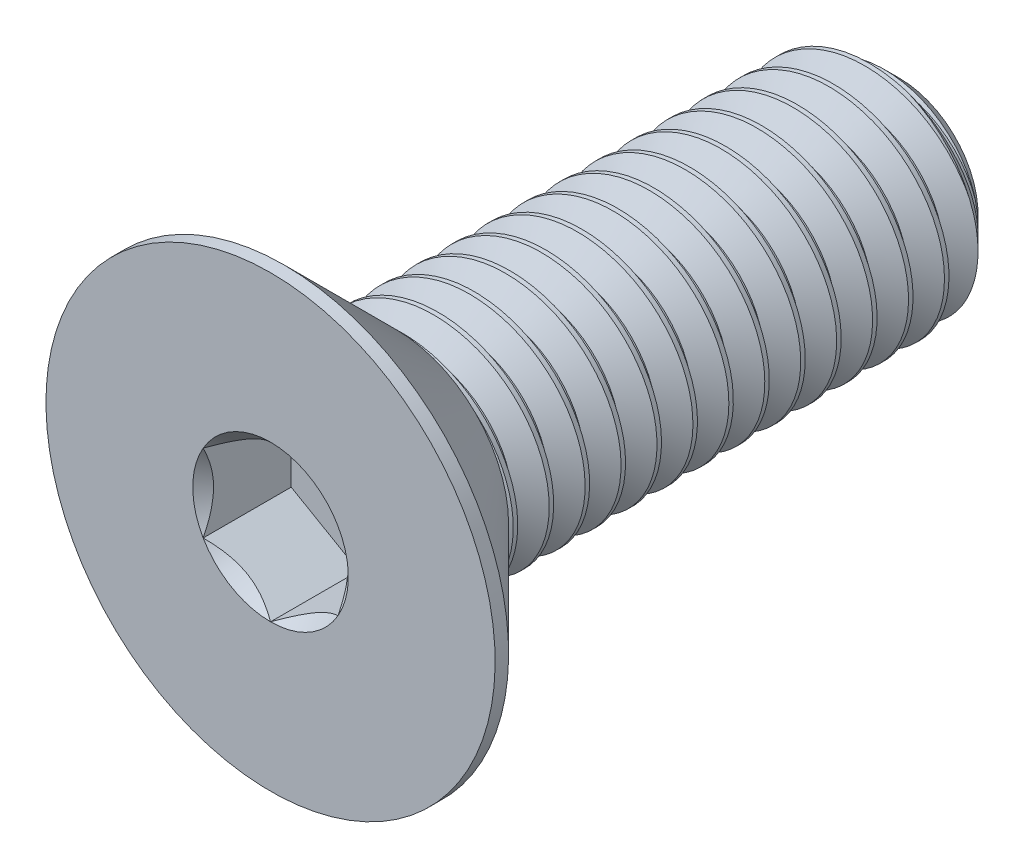
SolidWorks part; units mm, degrees
ref_plane "Front" through (0, 0, 0) normal (0, 0, 1) x (1, 0, 0)
ref_plane "Top" through (0, 0, 0) normal (0, 1, 0) x (1, 0, 0)
ref_plane "Right" through (0, 0, 0) normal (1, 0, 0) x (0, 0, -1)
sketch "Sketch1" plane through (0, 0, 0) normal (1, 0, 0) x (0, 0, -1)
  line L0 (-7, 5) -> (-6.7, 5) construction
  line L1 (-6.7, 5) -> (-4.2, 2.5) construction
  line L2 (-7, 2.5) -> (7, 2.5) construction
  line L3 (7, 2.5) -> (7, 0) construction
  line L4 (7, 0) -> (-7, 0) construction
  line L5 (-7, 0) -> (-7, 5) construction
  line L6 (-7, 5) -> (-7, -5) construction
  line L7 (7, 2.5) -> (7, -2.5) construction
  line L8 (-7, -5) -> (-6.7, -5) construction
  line L9 (-6.7, -5) -> (-4.2, -2.5) construction
  line L11 (-7, 2.5) -> (-7, 0) construction
  line L12 (-4.2, 2.5) -> (-4.2, 0) construction
  line L13 (6.95, 2.5866) -> (7.35, 1.8938) construction
  line L14 (7.35, 1.8938) -> (7.75, 2.5866) construction
  line L15 (7.75, 2.5866) -> (6.95, 2.5866) construction
  line L16 (7.35, 2.5866) -> (7.35, 2.5) construction
  line L17 (7.35, 2.5) -> (7.35, 1.9804) construction
  line L18 (7.35, 1.9804) -> (7.35, 1.8938) construction
  line L19 (7.35, 2.5433) -> (7.725, 2.5433) construction
  line L20 (7.35, 2.5433) -> (6.975, 2.5433) construction
  line L21 (7, 2.5) -> (7.7, 2.5) construction
  line L22 (7.3, 1.9804) -> (7.4, 1.9804) construction
  line L23 (7, -2.5) -> (-4.2, -2.5) construction
  point P10 (5, -2.5)
  point P24 (-4.2, 2.5)
  point P30 (0, 0)
  dimension "Head Diameter" = 10
  dimension "Head Height" = 2.8
  dimension "Length" = 14
  dimension "Countersink Angle" = 90
  dimension "Thread Pitch" = 0.8
  dimension "D2" = 0.1
  dimension "Minimum Thread Length" = 11.2
  dimension "Thread Size" = 5
  dimension "D1" = 2
sketch "Sketch2" plane through (0, 0, 0) normal (0, 0, 1) x (1, 0, 0)
  line L1 (0, 1.7321) -> (-1.5, 0.866) construction
  line L2 (-1.5, 0.866) -> (-1.5, -0.866) construction
  line L3 (-1.5, -0.866) -> (0, -1.7321) construction
  line L4 (0, -1.7321) -> (1.5, -0.866) construction
  line L5 (1.5, -0.866) -> (1.5, 0.866) construction
  line L6 (1.5, 0.866) -> (0, 1.7321) construction
  circle A0 centre (0, 0) radius 1.5 construction
  dimension "Drive Size" = 3
sketch "Sketch3" plane through (0, 0, 0) normal (1, 0, 0) x (0, 0, -1)
  line L0 (-7, 2.5) -> (7, 2.5)
  line L1 (7, 2.5) -> (7, 0)
  line L2 (7, 0) -> (-7, 0)
  line L3 (-7, 0) -> (-7, 2.5)
revolve "Revolve1" add sketch "Sketch3" angle 360 about L4
chamfer "Chamfer1" distance 0.75 angle 45 1 edges at (0, 2.5, -7)
sketch "Sketch6" plane through (0, 0, 0) normal (1, 0, 0) x (0, 0, -1)
  line L0 (-7, 5) -> (-6.7, 5)
  line L1 (-6.7, 5) -> (-4.2, 2.5)
  line L2 (-4.2, 2.5) -> (-4.2, 0)
  line L3 (-4.2, 0) -> (-7, 0)
  line L4 (-7, 0) -> (-7, 5)
revolve "Revolve2" add sketch "Sketch6" angle 360 about L4
sketch "Sketch8" plane through (0, 0, 7) normal (0, 0, 1) x (1, 0, 0)
  line L0 (0, 1.7321) -> (-1.5, 0.866) construction
  line L1 (1.5, 0.866) -> (0, 1.7321) construction
  line L2 (1.5, -0.866) -> (1.5, 0.866) construction
  line L3 (0, -1.7321) -> (1.5, -0.866) construction
  line L4 (-1.5, 0.866) -> (-1.5, -0.866) construction
  line L5 (-1.5, -0.866) -> (0, -1.7321) construction
  line L6 (0, 1.7321) -> (-1.5, 0.866)
  line L7 (1.5, 0.866) -> (0, 1.7321)
  line L8 (1.5, -0.866) -> (1.5, 0.866)
  line L9 (0, -1.7321) -> (1.5, -0.866)
  line L10 (-1.5, 0.866) -> (-1.5, -0.866)
  line L11 (-1.5, -0.866) -> (0, -1.7321)
extrude "Cut-Extrude1" cut sketch "Sketch8" against normal blind 1.96
sketch "Sketch9" plane through (0, 0, 7) normal (0, 0, 1) x (1, 0, 0)
  circle A0 centre (0, 0) radius 1.7321
extrude "Cut-Extrude2" cut sketch "Sketch9" against normal up to next (1.96 mm away) draft 45
ref_plane "Plane1" through (0, 0, 4.2) normal (0, 0, 1) x (1, 0, 0)
split "Split1" trim tools "Plane1" bodies to split 124 resulting bodies 126 127
sketch "Sketch4" plane through (0, 0, -7) normal (0, 0, -1) x (-1, 0, 0)
  circle A0 centre (0, 0) radius 2.5 construction
  circle A1 centre (0, 0) radius 2.5
curve "Helix/Spiral1" pitch 0.8 height 12 radius 2.5 centre (0, 0, -7) axis (0, 0, 1) start towards (0, 1, 0)
sketch "Sketch10" plane through (0, 0, 0) normal (1, 0, 0) x (0, 0, -1)
  line L0 (6.975, 2.5433) -> (7.725, 2.5433)
  line L1 (7.725, 2.5433) -> (7.4, 1.9804)
  line L2 (7.4, 1.9804) -> (7.3, 1.9804)
  line L3 (7.3, 1.9804) -> (6.975, 2.5433)
sweep "Cut-Sweep1" cut profiles "Sketch10" path "Helix/Spiral1"
equation "\"D2@Sketch1\" = \"Thread Pitch@Sketch1\" / 8"
equation "\"D4@Helix/Spiral1\"=\"Thread Pitch@Sketch1\""
equation "\"D3@Helix/Spiral1\"=\"Minimum Thread Length@Sketch1\"+\"Thread Pitch@Sketch1\""
equation "\"D1@Chamfer1\"=\"Thread Size@Sketch1\"*.15"
equation "\"D1@Cut-Extrude1\"=\"Head Height@Sketch1\"*.7"
equation "\"D1@Sketch1\"=\"Thread Pitch@Sketch1\"*2.5"
